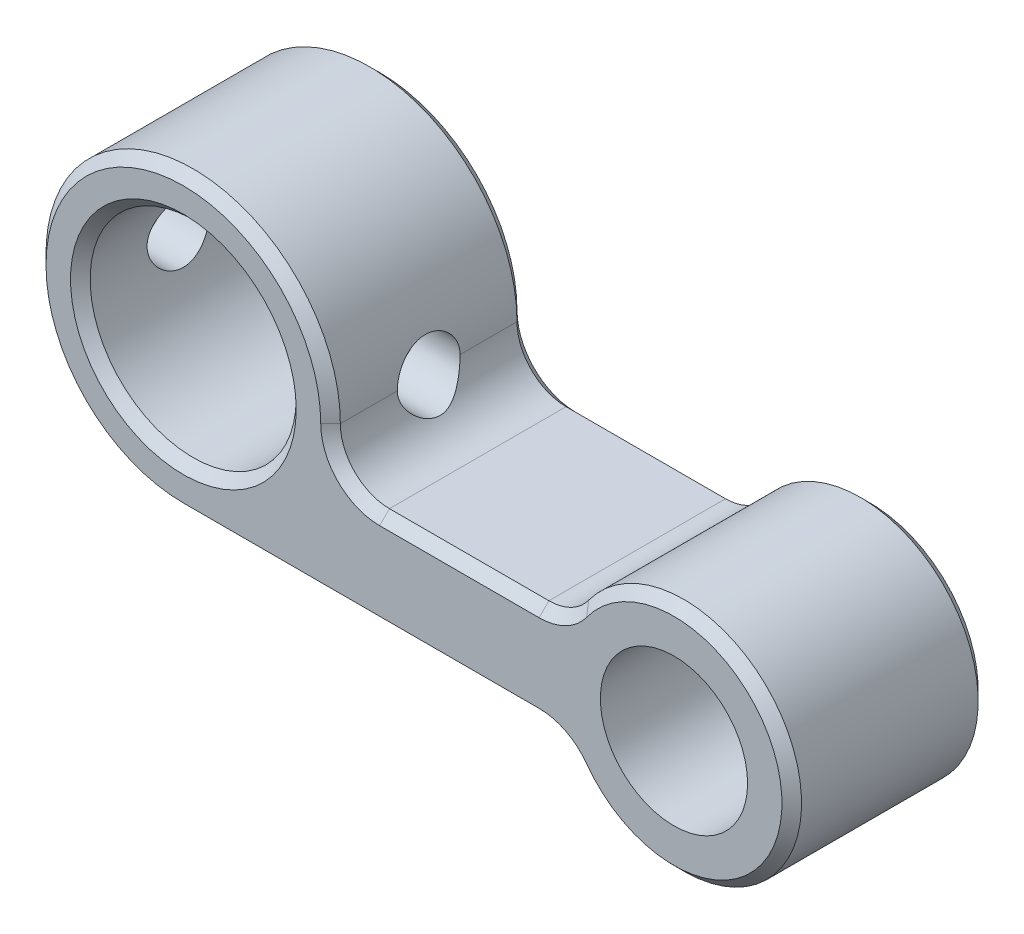
SolidWorks part; units mm, degrees
ref_plane "前视基准面" through (0, 0, 0) normal (0, 0, 1) x (1, 0, 0)
ref_plane "上视基准面" through (0, 0, 0) normal (0, 1, 0) x (1, 0, 0)
ref_plane "右视基准面" through (0, 0, 0) normal (1, 0, 0) x (0, 0, -1)
sketch "草图1" plane through (0, 0, 0) normal (0, 0, 1) x (1, 0, 0)
  circle A0 centre (0, 0) radius 10.5
  circle A1 centre (0, 0) radius 15
extrude "凸台-拉伸1" add sketch "草图1" along normal mid plane 20
sketch "草图2" plane through (0, 0, 0) normal (1, 0, 0) x (0, 0, -1)
  circle A0 centre (0, 0) radius 3.2
extrude "切除-拉伸1" cut sketch "草图2" against normal through all both and the other way through all
sketch "草图3" plane through (0, 0, 0) normal (0, 0, 1) x (1, 0, 0)
  line L0 (0, 0) -> (0, -15) construction
  line L1 (0, -15) -> (50, -15) construction
  line L2 (50, -15) -> (50, -10) construction
  line L3 (50, -10) -> (50, -5) construction
  line L4 (50, -10) -> (11.1803, -10) construction
  line L5 (50, -5) -> (14.1421, -5) construction
  line L6 (0, -15) -> (0, -20) construction
  line L7 (0, -20) -> (50, -20) construction
  line L8 (50, -20) -> (50, -15) construction
  circle A0 centre (0, 0) radius 15 construction
  circle A1 centre (50, -10) radius 5 construction
  circle A6 centre (50, -10) radius 12
  circle A7 centre (50, -10) radius 7.5
extrude "凸台-拉伸2" add sketch "草图3" along normal mid plane 20 separate body
sketch "草图4" plane through (0, 0, 0) normal (0, 0, 1) x (1, 0, 0)
  line L0 (0, 0) -> (0, -10) construction
  line L2 (40.202, -15) -> (0, -15)
  line L4 (40.202, -5) -> (14.1421, -5)
  arc A0 (0, -15) -> (14.1421, -5) centre (0, 0) ccw
  circle A2 centre (0, 0) radius 15 construction
  arc A3 (40.202, -5) -> (40.202, -15) centre (50, -10) ccw
extrude "凸台-拉伸3" add sketch "草图4" along normal mid plane 20
fillet "圆角1" radius 5 3 edges at (14.1421, -5, 0) (39.0913, -15, 0) (39.0913, -5, 0)
chamfer "倒角1" distance 1 angle 45 16 edges at (38.521, -15.5443, -10) (18.1261, -15, -10) (62, -10, -10) (-10.6066, 10.6066, -10) (38.521, -4.4557, -10) (16.4645, -3.5355, -10) (28.1261, -5, -10) (10.5, 0, -10) (10.5, 0, 10) (38.521, -4.4557, 10) (62, -10, 10) (28.1261, -5, 10) (38.521, -15.5443, 10) (16.4645, -3.5355, 10) (18.1261, -15, 10) (-10.6066, 10.6066, 10)
